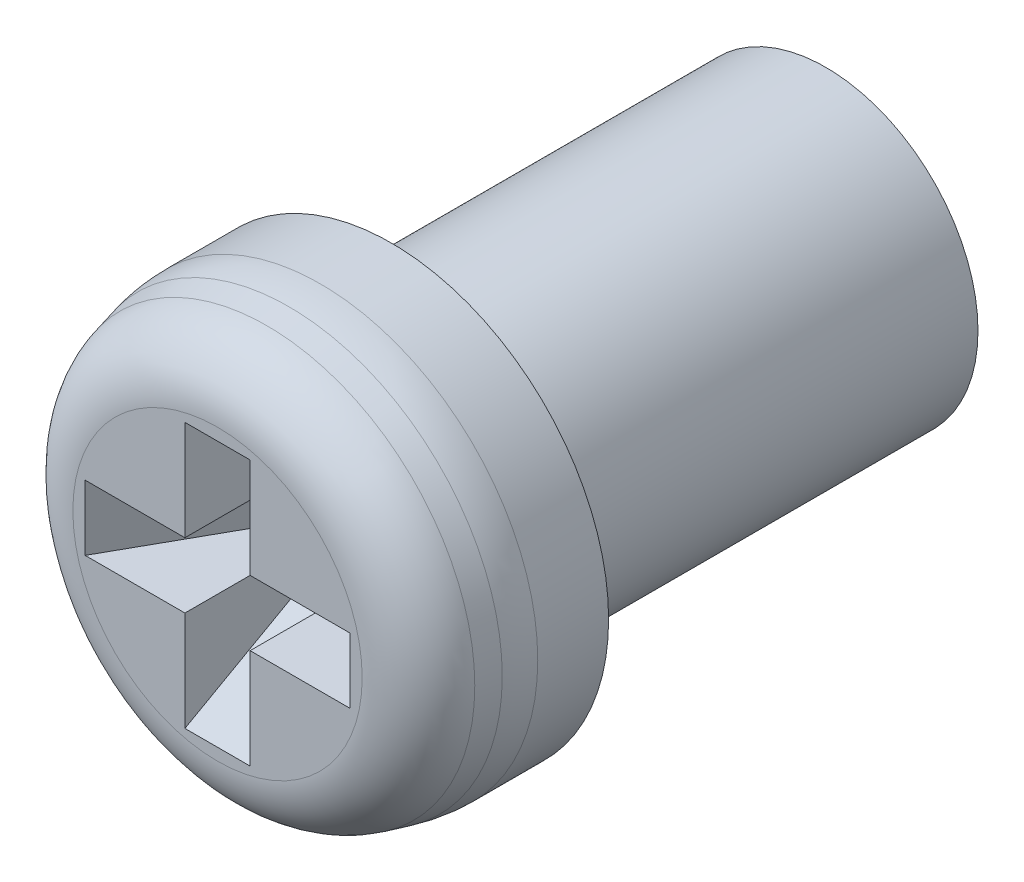
SolidWorks part; units mm, degrees
ref_plane "Płaszczyzna przednia" through (0, 0, 0) normal (0, 0, 1) x (1, 0, 0)
ref_plane "Płaszczyzna górna" through (0, 0, 0) normal (0, 1, 0) x (1, 0, 0)
ref_plane "Płaszczyzna prawa" through (0, 0, 0) normal (1, 0, 0) x (0, 0, -1)
sketch "Szkic1" plane through (0, 0, 0) normal (0, 0, 1) x (1, 0, 0)
  circle A0 centre (0, 0) radius 3.5
  dimension "D1" = 7
extrude "Dodanie-wyciągnięcie1" add sketch "Szkic1" along normal blind 10
ref_plane "Płaszczyzna2" through (0, 0, 10) normal (0, 0, 1) x (1, 0, 0)
sketch "Szkic3" plane through (0, 0, 10) normal (0, 0, 1) x (1, 0, 0)
  circle A0 centre (0, 0) radius 5
  dimension "D1" = 10
extrude "Dodanie-wyciągnięcie2" add sketch "Szkic3" along normal blind 4
chamfer "Sfazowanie2" distance 2 distance2 0.5 1 edges at (5, 0, 14) tangent propagation no first distance on face at (5, 0, 14)
fillet "Zaokrąglenie1" radius 1.5 1 edges at (4.5, 0, 14)
fillet "Zaokrąglenie2" radius 3 1 edges at (5, 0, 12)
fillet "Zaokrąglenie3" radius 0.5 1 edges at (3.5, 0, 10)
sketch "Szkic4" plane through (0, 0, 0) normal (0, 1, 0) x (1, 0, 0)
  line L0 (3.0459, -14) -> (-3.0459, -14)
  line L1 (-3.3288, -14) -> (3.3288, -14) construction
  line L2 (0, -9) -> (0.25, -9)
  line L3 (0, -9) -> (-0.25, -9)
  line L4 (-3.0459, -14) -> (-0.25, -9)
  line L5 (0.25, -9) -> (3.0459, -14)
  dimension "D1" = 0.25
  dimension "D2" = 0.25
  dimension "D3" = 5
  dimension "D4" = 2.7959
  dimension "D5" = 9
sketch "Szkic5" plane through (0, 0, 0) normal (1, 0, 0) x (0, 0, -1)
  line L5 (-9, 0) -> (-9, 0.25)
  line L6 (-9, 0) -> (-9, -0.25)
  line L7 (-14, 3.3288) -> (-14, -3.3288) construction
  line L8 (-14, -3.05) -> (-14, 3.05)
  line L9 (-14, 3.05) -> (-9, 0.25)
  line L10 (-9, -0.25) -> (-14, -3.05)
  dimension "D5" = 0.25
  dimension "D6" = 0.25
  dimension "D9" = 2.8
  dimension "D10" = 9
extrude "Wytnij-wyciągnięcie1" cut sketch "Szkic4" against normal blind 0.75 and the other way blind 0.75
extrude "Wytnij-wyciągnięcie2" cut sketch "Szkic5" against normal blind 0.75 and the other way blind 0.75
